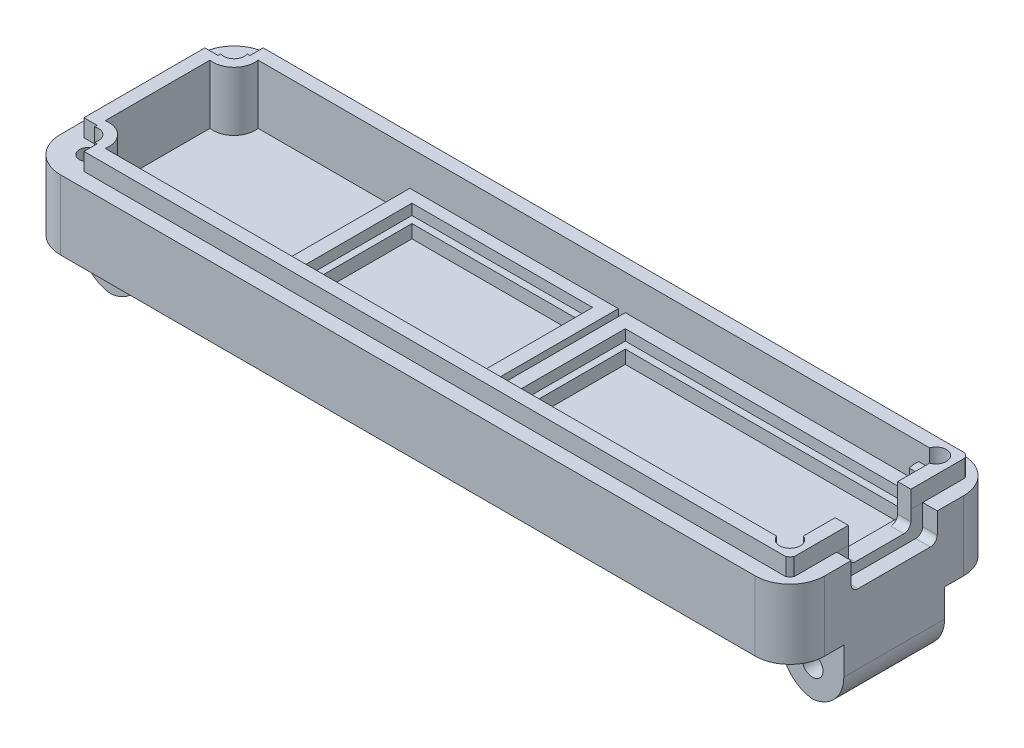
SolidWorks part; units mm, degrees
ref_plane "Front" through (0, 0, 0) normal (0, 0, 1) x (1, 0, 0)
ref_plane "Top" through (0, 0, 0) normal (0, 1, 0) x (1, 0, 0)
ref_plane "Right" through (0, 0, 0) normal (1, 0, 0) x (0, 0, -1)
sketch "Sketch1" plane through (0, 0, 0) normal (0, 1, 0) x (1, 0, 0)
  line L1 (-50.7685, 19.2221) -> (59.2315, 19.2221)
  line L2 (-50.7685, 19.2221) -> (-50.7685, -10.7779)
  line L3 (-50.7685, -10.7779) -> (59.2315, -10.7779)
  line L4 (59.2315, 19.2221) -> (59.2315, -10.7779)
  dimension "D1" = 110
  dimension "D2" = 30
extrude "Boss-Extrude1" add sketch "Sketch1" along normal blind 10
shell "Shell1" thickness 4 removed face at (4.2315, 10, -4.2221)
sketch "Sketch2" plane through (0, 4, 0) normal (0, 1, 0) x (1, 0, 0)
  line L0 (-19.4685, 13.5221) -> (6.5315, 13.5221) construction
  line L1 (6.5315, 13.5221) -> (6.5315, -5.0779) construction
  line L2 (6.5315, -5.0779) -> (-19.4685, -5.0779) construction
  line L3 (-19.4685, -5.0779) -> (-19.4685, 13.5221) construction
  line L4 (11.5315, 13.2221) -> (11.5315, -4.7779) construction
  line L5 (54.7315, 13.2221) -> (11.5315, 13.2221) construction
  line L6 (11.5315, -4.7779) -> (54.7315, -4.7779) construction
  line L7 (54.7315, -4.7779) -> (54.7315, 13.2221) construction
  line L8 (-19.4685, 13.5221) -> (6.5315, 13.5221)
  line L9 (6.5315, 13.5221) -> (6.5315, -5.0779)
  line L10 (6.5315, -5.0779) -> (-19.4685, -5.0779)
  line L11 (-19.4685, -5.0779) -> (-19.4685, 13.5221)
  line L12 (11.5315, 13.2221) -> (11.5315, -4.7779)
  line L13 (54.7315, 13.2221) -> (11.5315, 13.2221)
  line L14 (11.5315, -4.7779) -> (54.7315, -4.7779)
  line L15 (54.7315, -4.7779) -> (54.7315, 13.2221)
  line L16 (-21.4685, 15.5221) -> (8.5315, 15.5221)
  line L17 (8.5315, 15.5221) -> (8.5315, -7.0779)
  line L18 (8.5315, -7.0779) -> (-21.4685, -7.0779)
  line L19 (-21.4685, -7.0779) -> (-21.4685, 15.5221)
  line L20 (9.5315, 15.2221) -> (9.5315, -6.7779)
  line L21 (9.5315, -6.7779) -> (56.7315, -6.7779)
  line L22 (56.7315, -6.7779) -> (56.7315, 15.2221)
  line L23 (56.7315, 15.2221) -> (9.5315, 15.2221)
  dimension "D1" = 2
extrude "Boss-Extrude2" add sketch "Sketch2" along normal up to surface (3.45 mm away)
sketch "Sketch3" plane through (0, 4, 0) normal (0, 1, 0) x (1, 0, 0)
  line L0 (-19.4685, -5.0779) -> (-19.4685, 13.5221) construction
  line L1 (-19.4685, 13.5221) -> (6.5315, 13.5221) construction
  line L2 (6.5315, -5.0779) -> (-19.4685, -5.0779) construction
  line L3 (6.5315, 13.5221) -> (6.5315, -5.0779) construction
  line L4 (11.5315, -4.7779) -> (11.5315, 13.2221) construction
  line L5 (11.5315, 13.2221) -> (54.7315, 13.2221) construction
  line L6 (54.7315, -4.7779) -> (11.5315, -4.7779) construction
  line L7 (54.7315, -4.7779) -> (54.7315, 13.2221) construction
  line L8 (-19.4685, -5.0779) -> (-19.4685, 13.5221)
  line L9 (-19.4685, 13.5221) -> (6.5315, 13.5221)
  line L10 (6.5315, -5.0779) -> (-19.4685, -5.0779)
  line L11 (6.5315, 13.5221) -> (6.5315, -5.0779)
  line L12 (11.5315, -4.7779) -> (11.5315, 13.2221)
  line L13 (11.5315, 13.2221) -> (54.7315, 13.2221)
  line L14 (54.7315, -4.7779) -> (11.5315, -4.7779)
  line L15 (54.7315, -4.7779) -> (54.7315, 13.2221)
  line L16 (-18.4685, -4.0779) -> (-18.4685, 12.5221)
  line L17 (-18.4685, 12.5221) -> (5.5315, 12.5221)
  line L18 (5.5315, 12.5221) -> (5.5315, -4.0779)
  line L19 (5.5315, -4.0779) -> (-18.4685, -4.0779)
  line L20 (12.5315, -3.7779) -> (12.5315, 12.2221)
  line L21 (12.5315, 12.2221) -> (53.7315, 12.2221)
  line L22 (53.7315, -3.7779) -> (53.7315, 12.2221)
  line L23 (53.7315, -3.7779) -> (12.5315, -3.7779)
  dimension "D1" = 1
extrude "Boss-Extrude3" add sketch "Sketch3" along normal up to surface (1.91 mm away)
sketch "Sketch4" plane through (0, 10, 0) normal (0, 1, 0) x (1, 0, 0)
  line L0 (-46.2685, 23.7214) -> (-46.2685, -21.951) construction
  line L1 (4.2315, 28.0564) -> (4.2315, -26.286) construction
  line L2 (-56.4074, 14.7221) -> (67.1402, 14.7221) construction
  line L3 (-65.2104, 4.2221) -> (73.1379, 4.2221) construction
  line L4 (-50.7685, 19.2221) -> (-50.7685, -10.7779) construction
  line L5 (59.2315, 19.2221) -> (-50.7685, 19.2221) construction
  line L12 (55.2315, 11.7641) -> (55.2315, 13.3079)
  line L15 (51.9031, -5.2779) -> (53.6135, -5.2779)
  line L16 (55.2315, -4.8637) -> (55.2315, -3.3199)
  line L17 (51.9031, 13.7221) -> (53.6135, 13.7221)
  circle A0 centre (-46.2685, -6.2779) radius 3
  circle A1 centre (-46.2685, 14.7221) radius 3
  arc A2 (51.9031, 13.7221) -> (55.2315, 11.7641) centre (54.7315, 14.7221) cw
  arc A3 (51.9031, -5.2779) -> (55.2315, -3.3199) centre (54.7315, -6.2779) ccw
  circle A4 centre (-46.2685, 14.7221) radius 1.5
  circle A5 centre (-46.2685, -6.2779) radius 1.5
  arc A6 (53.6135, -5.2779) -> (55.2315, -4.8637) centre (54.7315, -6.2779) ccw
  arc A7 (53.6135, 13.7221) -> (55.2315, 13.3079) centre (54.7315, 14.7221) cw
  point P24 (11.5315, 13.2221)
  point P25 (54.7315, 13.2221)
  point P26 (54.7315, -4.7779)
  point P27 (11.5315, -4.7779)
  point P28 (11.5315, -5.2779)
  point P29 (55.2315, -5.2779)
  point P30 (55.2315, 13.7221)
  point P31 (11.5315, 13.7221)
  dimension "D3" = 3
  dimension "D1" = 4.5
  dimension "D2" = 4.5
extrude "Boss-Extrude4" add sketch "Sketch4" against normal up to surface (6 mm away) up to face at (-34.1185, 4, -4.2221)
sketch "Sketch5" plane through (0, 10, 0) normal (0, 1, 0) x (1, 0, 0)
  line L0 (-65.2104, 4.2221) -> (73.1379, 4.2221) construction
  line L1 (-65.2104, 4.2221) -> (73.1379, 4.2221) construction
  line L2 (4.2315, 28.0564) -> (4.2315, -26.286) construction
  line L3 (4.2315, 28.0564) -> (4.2315, -26.286) construction
  circle A0 centre (-46.2685, 14.7221) radius 1.25
  circle A1 centre (-46.2685, -6.2779) radius 1.25
  circle A2 centre (54.7315, -6.2779) radius 1.25
  circle A3 centre (54.7315, 14.7221) radius 1.25
  dimension "D1" = 2.5
extrude "Cut-Extrude4" cut sketch "Sketch5" against normal up to surface (10 mm away) up to face at (4.2315, 0, -4.2221)
sketch "Sketch7" plane through (0, 10, 0) normal (0, 1, 0) x (1, 0, 0)
  line L0 (-46.7685, 11.7641) -> (-46.7685, -3.3199) construction
  line L1 (-46.7685, 13.3079) -> (-46.7685, 12.9221)
  line L2 (51.7734, 15.2221) -> (-43.3105, 15.2221) construction
  line L3 (-43.3105, -6.7779) -> (51.7734, -6.7779) construction
  line L4 (55.2315, -5.1322) -> (55.2315, 13.5765) construction
  line L5 (51.7734, 15.2221) -> (-43.3105, 15.2221)
  line L6 (-43.3105, -6.7779) -> (51.7734, -6.7779)
  line L7 (55.2315, -4.8637) -> (55.2315, 13.3079)
  line L8 (51.7734, 15.2221) -> (53.3173, 15.2221)
  line L10 (51.7734, -6.7779) -> (53.3173, -6.7779)
  line L12 (-44.4685, -6.7779) -> (-44.8543, -6.7779)
  line L13 (-46.7685, -4.8637) -> (-46.7685, -4.4779)
  line L14 (-48.6685, 12.9221) -> (-48.6685, -3.3199)
  line L15 (-48.6685, -4.4779) -> (-48.6685, -3.3199)
  line L16 (-43.3105, -8.6779) -> (-44.4685, -8.6779)
  line L17 (-43.3105, -8.6779) -> (51.7734, -8.6779)
  line L18 (51.7734, -8.6779) -> (56.5315, -8.6779)
  line L19 (57.1315, -8.0779) -> (57.1315, -5.1322)
  line L20 (57.1315, -5.1322) -> (57.1315, 13.5765)
  line L21 (57.1315, 16.5221) -> (57.1315, 13.5765)
  line L22 (51.7734, 17.1221) -> (56.5315, 17.1221)
  line L23 (51.7734, 17.1221) -> (-44.4685, 17.1221)
  line L24 (-48.6685, 12.9221) -> (-46.7685, 12.9221)
  line L25 (-46.7685, 15.2221) -> (-46.7685, -3.3199) construction
  line L26 (51.7734, 17.1221) -> (-48.6685, 17.1221) construction
  line L27 (-48.6685, 17.1221) -> (-48.6685, -3.3199) construction
  line L28 (51.7734, 15.2221) -> (-46.7685, 15.2221) construction
  line L29 (-44.4685, 17.1221) -> (-44.4685, 15.2221)
  line L30 (-46.7685, 11.7641) -> (-46.7685, -3.3199)
  line L31 (-44.4685, 15.2221) -> (-44.8543, 15.2221)
  line L32 (-48.6685, -4.4779) -> (-46.7685, -4.4779)
  line L33 (-43.3105, -6.7779) -> (-46.7685, -6.7779) construction
  line L34 (-43.3105, -8.6779) -> (-48.6685, -8.6779) construction
  line L35 (-48.6685, -8.6779) -> (-48.6685, -3.3199) construction
  line L36 (-46.7685, -6.7779) -> (-46.7685, -3.3199) construction
  line L37 (-44.4685, -8.6779) -> (-44.4685, -6.7779)
  line L38 (55.2315, -5.1322) -> (55.2315, 13.5765) construction
  line L39 (51.7734, -8.6779) -> (57.1315, -8.6779) construction
  line L40 (57.1315, -8.6779) -> (57.1315, -5.1322) construction
  line L41 (57.1315, 17.1221) -> (57.1315, 13.5765) construction
  line L42 (51.7734, 17.1221) -> (57.1315, 17.1221) construction
  line L43 (51.7734, -6.7779) -> (55.2315, -6.7779) construction
  line L44 (55.2315, -6.7779) -> (55.2315, -5.1322) construction
  line L45 (51.7734, 15.2221) -> (55.2315, 15.2221) construction
  line L46 (55.2315, 15.2221) -> (55.2315, 13.5765) construction
  circle A0 centre (-46.2685, 14.7221) radius 3 construction
  arc A1 (-46.7685, 11.7641) -> (-43.3105, 15.2221) centre (-46.2685, 14.7221) ccw
  circle A2 centre (-46.2685, 14.7221) radius 1.5 construction
  arc A3 (-46.7685, 13.3079) -> (-44.8543, 15.2221) centre (-46.2685, 14.7221) ccw
  circle A4 centre (-46.2685, -6.2779) radius 3 construction
  circle A5 centre (-46.2685, -6.2779) radius 1.5 construction
  arc A7 (55.2315, 13.3079) -> (53.6135, 13.7221) centre (54.7315, 14.7221) ccw construction
  arc A8 (51.9031, -5.2779) -> (55.2315, -3.3199) centre (54.7315, -6.2779) ccw construction
  arc A9 (53.6135, -5.2779) -> (55.2315, -4.8637) centre (54.7315, -6.2779) ccw construction
  arc A10 (-43.3105, -6.7779) -> (-46.7685, -3.3199) centre (-46.2685, -6.2779) ccw
  arc A11 (-44.8543, -6.7779) -> (-46.7685, -4.8637) centre (-46.2685, -6.2779) ccw
  arc A13 (55.2315, 13.3079) -> (53.3173, 15.2221) centre (54.7315, 14.7221) ccw
  arc A14 (51.7734, -6.7779) -> (52.9315, -8.6779) centre (54.7315, -6.2779) ccw
  arc A15 (53.3173, -6.7779) -> (55.2315, -4.8637) centre (54.7315, -6.2779) ccw
  arc A16 (56.5315, -8.6779) -> (57.1315, -8.0779) centre (54.7315, -6.2779) ccw
  arc A18 (57.1315, 16.5221) -> (56.5315, 17.1221) centre (54.7315, 14.7221) ccw
  dimension "D1" = 1.9
extrude "Boss-Extrude5" add sketch "Sketch7" along normal blind 2.5
sketch "Sketch8" plane through (0, 0, 0) normal (0, -1, 0) x (1, 0, 0)
  line L0 (4.2315, 26.286) -> (4.2315, -28.0564) construction
  line L1 (-65.2104, -4.2221) -> (73.1379, -4.2221) construction
  line L2 (-65.2104, -4.2221) -> (73.1379, -4.2221) construction
  line L3 (-43.5185, -13.1344) -> (-43.5185, -16.3098)
  line L4 (-43.5185, 7.8656) -> (-46.2685, 9.4533)
  line L5 (-46.2685, 9.4533) -> (-49.0185, 7.8656)
  line L6 (-49.0185, 7.8656) -> (-49.0185, 4.6902)
  line L7 (-49.0185, 4.6902) -> (-46.2685, 3.1025)
  line L8 (-46.2685, 3.1025) -> (-43.5185, 4.6902)
  line L9 (-43.5185, 4.6902) -> (-43.5185, 7.8656)
  line L10 (-46.2685, -11.5467) -> (-43.5185, -13.1344)
  line L11 (-49.0185, -13.1344) -> (-46.2685, -11.5467)
  line L12 (-49.0185, -16.3098) -> (-49.0185, -13.1344)
  line L13 (-46.2685, -17.8975) -> (-49.0185, -16.3098)
  line L14 (-43.5185, -16.3098) -> (-46.2685, -17.8975)
  line L15 (51.9815, -16.3098) -> (54.7315, -17.8975)
  line L16 (54.7315, -17.8975) -> (57.4815, -16.3098)
  line L17 (57.4815, -16.3098) -> (57.4815, -13.1344)
  line L18 (57.4815, -13.1344) -> (54.7315, -11.5467)
  line L19 (54.7315, -11.5467) -> (51.9815, -13.1344)
  line L20 (51.9815, 4.6902) -> (51.9815, 7.8656)
  line L21 (54.7315, 3.1025) -> (51.9815, 4.6902)
  line L22 (57.4815, 4.6902) -> (54.7315, 3.1025)
  line L23 (57.4815, 7.8656) -> (57.4815, 4.6902)
  line L24 (54.7315, 9.4533) -> (57.4815, 7.8656)
  line L25 (51.9815, 7.8656) -> (54.7315, 9.4533)
  line L26 (51.9815, -13.1344) -> (51.9815, -16.3098)
  circle A0 centre (-46.2685, 6.2779) radius 2.75 construction
  circle A1 centre (-46.2685, -14.7221) radius 2.75 construction
  circle A2 centre (54.7315, -14.7221) radius 2.75 construction
  circle A3 centre (54.7315, 6.2779) radius 2.75 construction
  dimension "D1" = 5.5
extrude "Cut-Extrude7" cut sketch "Sketch8" against normal blind 3
sketch "Sketch9" plane through (0, 12.5, 0) normal (0, 1, 0) x (1, 0, 0)
  line L0 (73.1379, 4.2221) -> (39.6079, 4.2221) construction
  line L2 (52.1315, 8.7221) -> (63.7439, 8.7221)
  line L3 (52.1315, 8.7221) -> (52.1315, -0.2779)
  line L4 (52.1315, -0.2779) -> (63.7439, -0.2779)
  line L5 (63.7439, 8.7221) -> (63.7439, -0.2779)
  dimension "D1" = 9
  dimension "D2" = 4.5
extrude "Cut-Extrude8" cut sketch "Sketch9" against normal up to surface (5.05 mm away) up to face at (46.8706, 7.45, -4.2221)
sketch "Sketch10" plane through (0, 10, 0) normal (0, 1, 0) x (1, 0, 0)
  line L0 (73.1379, 4.2221) -> (33.2546, 4.2221) construction
  line L1 (-65.2104, 4.2221) -> (73.1379, 4.2221) construction
  line L2 (59.2315, 8.7221) -> (59.2315, 19.2221) construction
  line L4 (57.1264, -1.9731) -> (57.1264, 10.4173)
  line L5 (57.1264, 10.4173) -> (59.2315, 10.4173)
  line L6 (59.2315, -1.9731) -> (59.2315, 10.4173)
  line L7 (57.1264, -1.9731) -> (59.2315, -1.9731)
extrude "Cut-Extrude9" cut sketch "Sketch10" against normal blind 4
fillet "Fillet1" radius 5 4 edges at (59.2315, 5, -19.2221) (59.2315, 5, 10.7779) (-50.7685, 5, -19.2221) (-50.7685, 5, 10.7779)
fillet "Fillet2" radius 1 4 edges at (56.179, 7.45, 0.2779) (56.179, 7.45, -8.7221) (58.179, 6, -10.4173) (58.179, 6, 1.9731)
sketch "Sketch11" plane through (0, 0, 0) normal (0, -1, 0) x (-1, 0, 0)
  line L0 (-59.2315, 4.2221) -> (62.6729, 4.2221) construction
  line L1 (-59.2315, -5.7779) -> (-59.2315, 14.2221) construction
  line L2 (-54.7315, -6.2779) -> (-54.7315, 14.8939) construction
  line L3 (-4.2315, -10.7779) -> (-4.2315, 19.2221) construction
  line L4 (-4.2315, -22.9797) -> (-4.2315, 29.4117) construction
  line L5 (-50.2315, -3.0279) -> (-59.2315, -3.0279)
  line L6 (41.7685, 11.4721) -> (41.7685, -3.0279)
  line L7 (-50.2315, 11.4721) -> (-59.2315, 11.4721)
  line L8 (45.7685, -10.7779) -> (-54.2315, -10.7779) construction
  line L9 (-54.2315, 19.2221) -> (45.7685, 19.2221) construction
  line L11 (-50.2315, -3.0279) -> (-50.2315, 11.4721)
  line L12 (-59.2315, -3.0279) -> (-59.2315, 11.4721)
  line L15 (50.7685, -3.0279) -> (50.7685, 11.4721)
  line L16 (41.7685, 11.4721) -> (50.7685, 11.4721)
  line L18 (41.7685, -3.0279) -> (50.7685, -3.0279)
  dimension "D1" = 9
  dimension "D3" = 14.5
  dimension "D4" = 7.25
extrude "Boss-Extrude6" add sketch "Sketch11" along normal blind 9
sketch "Sketch12" plane through (0, 0, 3.0279) normal (0, 0, 1) x (1, 0, 0)
  line L0 (50.2315, -4.75) -> (59.2315, -4.75) construction
  line L3 (54.7315, -9) -> (54.7315, 0) construction
  line L4 (59.2315, -9) -> (50.2315, -9) construction
  line L5 (59.2315, 0) -> (50.2315, 0) construction
  line L6 (4.2315, 28.6454) -> (4.2315, -29.5482) construction
  line L7 (-46.2685, -9) -> (-46.2685, 0) construction
  line L8 (-41.7685, -4.75) -> (-50.7685, -4.75) construction
  circle A0 centre (54.7315, -4.75) radius 1.5
  circle A1 centre (-46.2685, -4.75) radius 1.5
  point P2 (0, 0)
  point P3 (54.7315, -4.75)
  dimension "D1" = 3
  dimension "D2" = 4.75
  dimension "D3" = 4.75
extrude "Cut-Extrude10" cut sketch "Sketch12" against normal up to surface (14.5 mm away) up to face at (54.7315, -4.5, -11.4721)
fillet "Fillet3" radius 5 4 edges at (-50.7685, -9, -4.2221) (59.2315, -9, -4.2221) (50.2315, -9, -4.2221) (-41.7685, -9, -4.2221)
